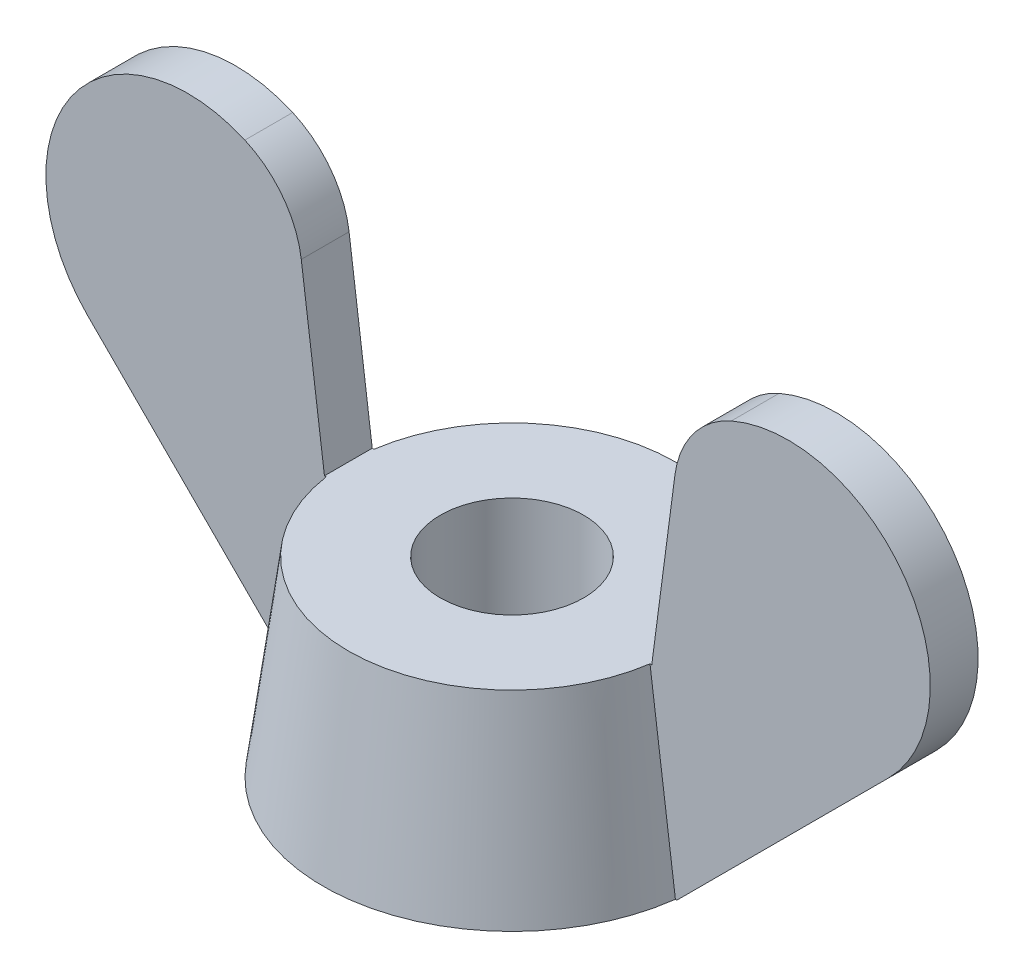
SolidWorks part; units mm, degrees
ref_plane "前视基准面" through (0, 0, 0) normal (0, 0, 1) x (1, 0, 0)
ref_plane "上视基准面" through (0, 0, 0) normal (0, 1, 0) x (1, 0, 0)
ref_plane "右视基准面" through (0, 0, 0) normal (1, 0, 0) x (0, 0, -1)
sketch "草图1" plane through (0, 0, 0) normal (0, 1, 0) x (1, 0, 0)
  circle A0 centre (0, 0) radius 3.95
  dimension "D1" = 7.9
extrude "凸台-拉伸1" add sketch "草图1" along normal blind 4 draft 7.5 contours A0
sketch "草图2" plane through (0, 0, 0) normal (0, 1, 0) x (1, 0, 0)
  circle A0 centre (0, 0) radius 1.5
  dimension "D1" = 3
extrude "切除-拉伸1" cut sketch "草图2" along normal blind 4
sketch "草图3" plane through (0, 0, 0) normal (0, 0, 1) x (1, 0, 0)
  line L0 (0, 0) -> (0, 9.5) construction
  line L1 (-3.95, 0) -> (3.95, 0) construction
  line L2 (0, 9.5) -> (9.25, 9.5) construction
  line L3 (9.25, 9.5) -> (9.25, 0) construction
  line L4 (9.25, 0) -> (0, 0) construction
  line L5 (3.95, 0) -> (9.25, 5.3) construction
  line L6 (3.95, 0) -> (3.4234, 4) construction
  line L7 (3.4234, 4) -> (4.1475, 9.5) construction
  line L8 (8.3802, 4.4302) -> (3.95, 0)
  line L9 (3.9078, 7.6794) -> (3.4234, 4)
  line L14 (3.4234, 4) -> (1.95, 4)
  line L15 (3.4234, 4) -> (-3.4234, 4) construction
  line L16 (1.95, 4) -> (1.95, 0)
  line L17 (1.95, 0) -> (3.95, 0)
  line L18 (-1.95, 4) -> (-1.95, 0)
  line L19 (-3.4234, 4) -> (-1.95, 4)
  line L20 (-3.9078, 7.6794) -> (-3.4234, 4)
  line L21 (-8.3802, 4.4302) -> (-3.95, 0)
  line L22 (-1.95, 0) -> (-3.95, 0)
  arc A0 (5.0875, 9.25) -> (8.3802, 4.4302) centre (6.2802, 6.5302) cw
  arc A1 (3.9078, 7.6794) -> (5.0875, 9.25) centre (5.8907, 7.4184) cw
  arc A2 (-3.9078, 7.6794) -> (-5.0875, 9.25) centre (-5.8907, 7.4184) ccw
  arc A3 (-5.0875, 9.25) -> (-8.3802, 4.4302) centre (-6.2802, 6.5302) ccw
  point P18 (4.0083, 8.4429)
  point P32 (0, 0)
  point P33 (0, 0)
  dimension "D5" = 2
  dimension "D1" = 9.25
  dimension "D2" = 9.5
  dimension "D3" = 45
  dimension "D4" = 7.5
  dimension "D6" = 2
extrude "凸台-拉伸2" add sketch "草图3" along normal mid plane 1
